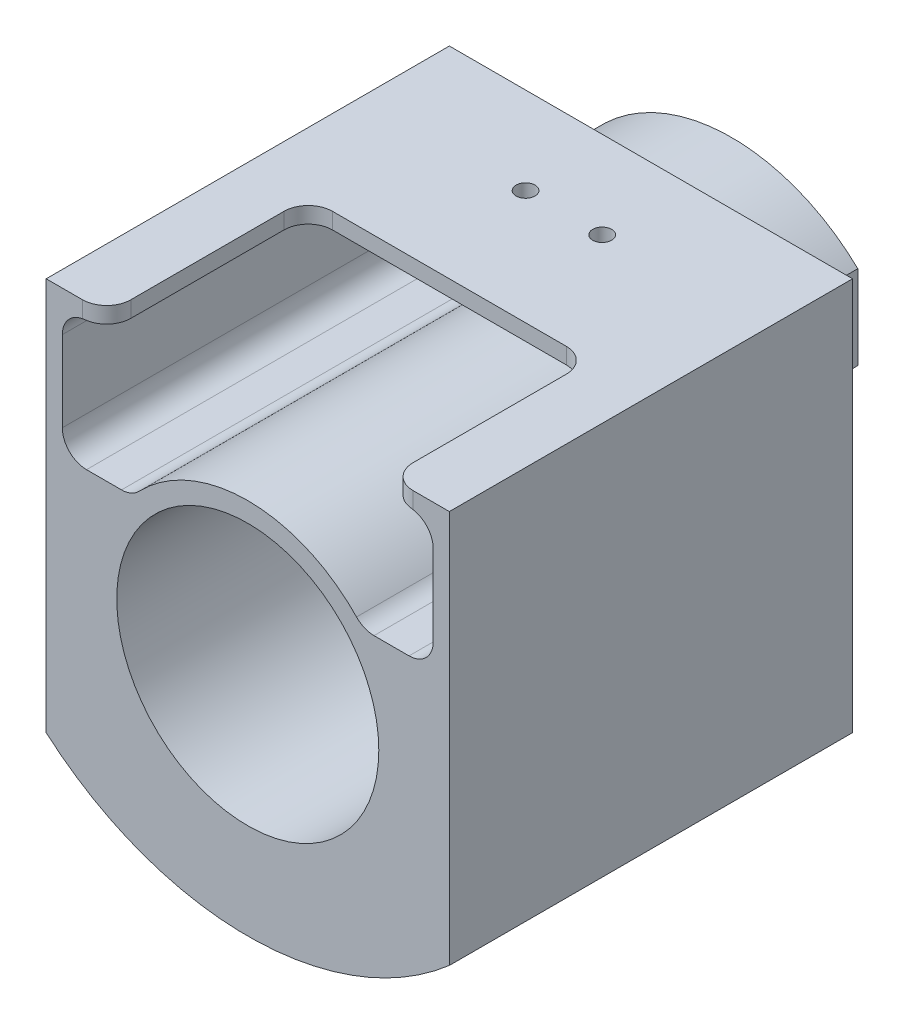
SolidWorks part; units mm, degrees
ref_plane "Front Plane" through (0, 0, 0) normal (0, 0, 1) x (1, 0, 0)
ref_plane "Top Plane" through (0, 0, 0) normal (0, 1, 0) x (1, 0, 0)
ref_plane "Right Plane" through (0, 0, 0) normal (1, 0, 0) x (0, 0, -1)
sketch "Sketch1" plane through (0, 0, 0) normal (0, 0, 1) x (1, 0, 0)
  line L1 (0, 0) -> (0, -38.1) construction
  line L2 (-25, 0) -> (-25, -28.7508)
  line L3 (25, 0) -> (25, -28.7508)
  line L4 (-25, 0) -> (-25, 20)
  line L5 (-25, 20) -> (25, 20)
  line L6 (25, 20) -> (25, 0)
  arc A0 (-25, -28.7508) -> (25, -28.7508) centre (0, 0) ccw
  dimension "D1" = 76.2
  dimension "D2" = 50
  dimension "D3" = 20
extrude "Boss-Extrude2" add sketch "Sketch1" along normal blind 50
sketch "Sketch2" plane through (0, 0, 50) normal (0, 0, 1) x (1, 0, 0)
  line L6 (0, 6.25) -> (0, -26.25) construction
  circle A0 centre (0, -10) radius 16.25
  dimension "D2" = 32.5
  dimension "D1" = 10
extrude "Cut-Extrude1" cut sketch "Sketch2" against normal through all both
sketch "Sketch4" plane through (0, 0, 50) normal (0, 0, 1) x (1, 0, 0)
  line L0 (-23, 18) -> (23, 18)
  line L3 (0, 20) -> (0, 6.25) construction
  line L4 (25, 20) -> (-25, 20) construction
  line L5 (23, 2) -> (14.3178, 2)
  line L6 (-23, 18) -> (-23, 2)
  line L7 (-23, 2) -> (-14.3178, 2)
  line L8 (-25, 20) -> (-25, -28.7508) construction
  line L9 (23, 18) -> (23, 2)
  circle A2 centre (0, -10) radius 16.25 construction
  arc A3 (14.3178, 2) -> (-14.3178, 2) centre (0, -10) ccw
  point P2 (0, 13.125)
  point P14 (0, 18)
  dimension "D1" = 37.3631
  dimension "D2" = 2
  dimension "D3" = 2
  dimension "D4" = 16
extrude "Cut-Extrude3" cut sketch "Sketch4" against normal through all
fillet "Fillet1" radius 3 6 edges at (23, 18, 25) (23, 2, 25) (14.3178, 2, 25) (-14.3178, 2, 25) (-23, 2, 25) (-23, 18, 25)
sketch "Sketch5" plane through (0, 20, 0) normal (0, 1, 0) x (1, 0, 0)
  line L0 (25, -50) -> (-25, -50) construction
  line L1 (-17.5, -50) -> (17.5, -50)
  line L2 (-17.5, -50) -> (-17.5, -25)
  line L3 (-17.5, -25) -> (17.5, -25)
  line L4 (17.5, -50) -> (17.5, -25)
  line L5 (0, 0) -> (0, -50) construction
  dimension "D1" = 35
  dimension "D2" = 25
extrude "Cut-Extrude4" cut sketch "Sketch5" against normal blind 10
fillet "Fillet2" radius 3 4 edges at (17.5, 19, 50) (17.5, 19, 25) (-17.5, 19, 25) (-17.5, 19, 50)
ref_plane "Plane1" through (0, 0, 14) normal (0, 0, 1) x (1, 0, 0)
sketch "Sketch6" plane through (0, 0, 14) normal (0, 0, 1) x (1, 0, 0)
  line L0 (0, -10) -> (0, 3) construction
  line L1 (0, -10) -> (-4.4463, 2.216) construction
  circle A1 centre (0, -10) radius 16.25 construction
  circle A3 centre (0, -10) radius 9.5
  circle A8 centre (0, -10) radius 16.25
  circle A9 centre (0, -10) radius 13 construction
  circle A10 centre (-4.4463, 2.216) radius 1.65
  circle A11 centre (12.216, -5.5537) radius 1.65
  circle A12 centre (4.4463, -22.216) radius 1.65
  circle A13 centre (-12.216, -14.4463) radius 1.65
  dimension "D1" = 19
  dimension "D6" = 13
  dimension "D2" = 3.5
  dimension "D3" = 3.3
  dimension "D4" = 20
  dimension "D5" = 4
extrude "Boss-Extrude3" add sketch "Sketch6" against normal blind 5
sketch "Sketch7" plane through (0, 0, 0) normal (1, 0, 0) x (0, 0, -1)
  circle A0 centre (-40, -32) radius 2.25
  circle A1 centre (-10, -32) radius 2.25
  dimension "D3" = 4.5
  dimension "D1" = 32
  dimension "D2" = 10
  dimension "D4" = 30
extrude "Cut-Extrude5" cut sketch "Sketch7" against normal through all both and the other way through all
sketch "Sketch8" plane through (0, 20, 0) normal (0, 1, 0) x (1, 0, 0)
  line L0 (0, 0) -> (0, -25) construction
  line L1 (25, 0) -> (-25, 0) construction
  line L2 (14.5, -25) -> (-14.5, -25) construction
  circle A0 centre (-4.75, -10.8) radius 1.175
  circle A1 centre (4.75, -10.8) radius 1.175
  dimension "D1" = 2.35
  dimension "D2" = 9.5
  dimension "D3" = 10.8
extrude "Cut-Extrude6" cut sketch "Sketch8" against normal up to next contours A0 | A1
sketch "Sketch9" plane through (0, 0, 50) normal (0, 0, 1) x (1, 0, 0)
  line L0 (0, -28.5) -> (0, -5) construction
  line L1 (0, -10) -> (0, -28.5) construction
  line L2 (-15.6553, 2) -> (-15.6553, 11.4123)
  line L3 (15.6553, 2) -> (15.6553, 11.4123)
  line L4 (0, 8.6815) -> (0, 17.6815) construction
  line L5 (-14.6553, 2.1716) -> (-14.6553, 10.5325)
  line L6 (14.6553, 2.1716) -> (14.6553, 10.5325)
  line L7 (-15.6553, 2) -> (-15.6553, 1)
  line L8 (15.6553, 2) -> (15.6553, 1)
  line L9 (14.6553, 2) -> (14.6553, 10.9784) construction
  line L10 (-14.6553, 2) -> (-14.6553, 10.9784) construction
  arc A0 (13.4892, 2.9245) -> (-13.4892, 2.9245) centre (0, -10) ccw construction
  arc A1 (13.4892, 2.9245) -> (-13.4892, 2.9245) centre (0, -10) ccw
  arc A3 (-15.6553, 11.4123) -> (15.6553, 11.4123) centre (0, -5) cw
  arc A4 (13.4892, 2.9245) -> (15.6553, 2) centre (15.6553, 5) ccw construction
  arc A5 (-15.6553, 2) -> (-13.4892, 2.9245) centre (-15.6553, 5) ccw construction
  arc A6 (13.4892, 2.9245) -> (15.6553, 2) centre (15.6553, 5) ccw
  arc A7 (-15.6553, 2) -> (-13.4892, 2.9245) centre (-15.6553, 5) ccw
  arc A8 (12.7671, 2.2327) -> (15.6553, 1) centre (15.6553, 5) ccw
  arc A9 (12.7671, 2.2327) -> (-12.7671, 2.2327) centre (0, -10) ccw
  arc A10 (-15.6553, 1) -> (-12.7671, 2.2327) centre (-15.6553, 5) ccw
  arc A11 (-14.3156, 11.2835) -> (14.3156, 11.2835) centre (0, -5) cw
  arc A12 (-14.6553, 10.9784) -> (14.6553, 10.9784) centre (0, -5) cw construction
  arc A13 (14.6553, 10.5325) -> (14.3156, 11.2835) centre (13.6553, 10.5325) ccw
  arc A14 (-14.6553, 10.5325) -> (-14.3156, 11.2835) centre (-13.6553, 10.5325) cw
  point P26 (0, 0)
  point P28 (0, 0)
  dimension "D1" = 9
  dimension "D2" = 1
  dimension "D4" = 1
  dimension "Ring Gear Outer Dia to Center" = 23.5
  dimension "Pinion to Ring Gear Outer Diameter" = 18.5
  dimension "D3" = 1
extrude "Boss-Extrude4" add sketch "Sketch9" along normal blind 8 and the other way blind 10 from surface contours L5 A11 L6 L2 L3 A3 A6 | L7 A10 A9 A8 L8 L2 L3 A6 region at (-15.0935, 1.7255, 50) region at (-15.3051, 6.7061, 50) starting at face at (0, 7.9303, 0)
fillet "Fillet5" radius 0.25 8 edges at (14.0281, 2.4797, -10) (-14.0281, 2.4797, -10) (14.6553, 6.352, -10) (14.5664, 10.9446, -10) (-14.6553, 6.352, -10) (-14.5664, 10.9446, -10) (0, 8.6815, -10) (0, 16.6815, -10)
fillet "Fillet6" radius 0.25 5 edges at (14.6553, 6.352, 8) (14.5664, 10.9446, 8) (-14.6553, 6.352, 8) (-14.5664, 10.9446, 8) (0, 16.6815, 8)
